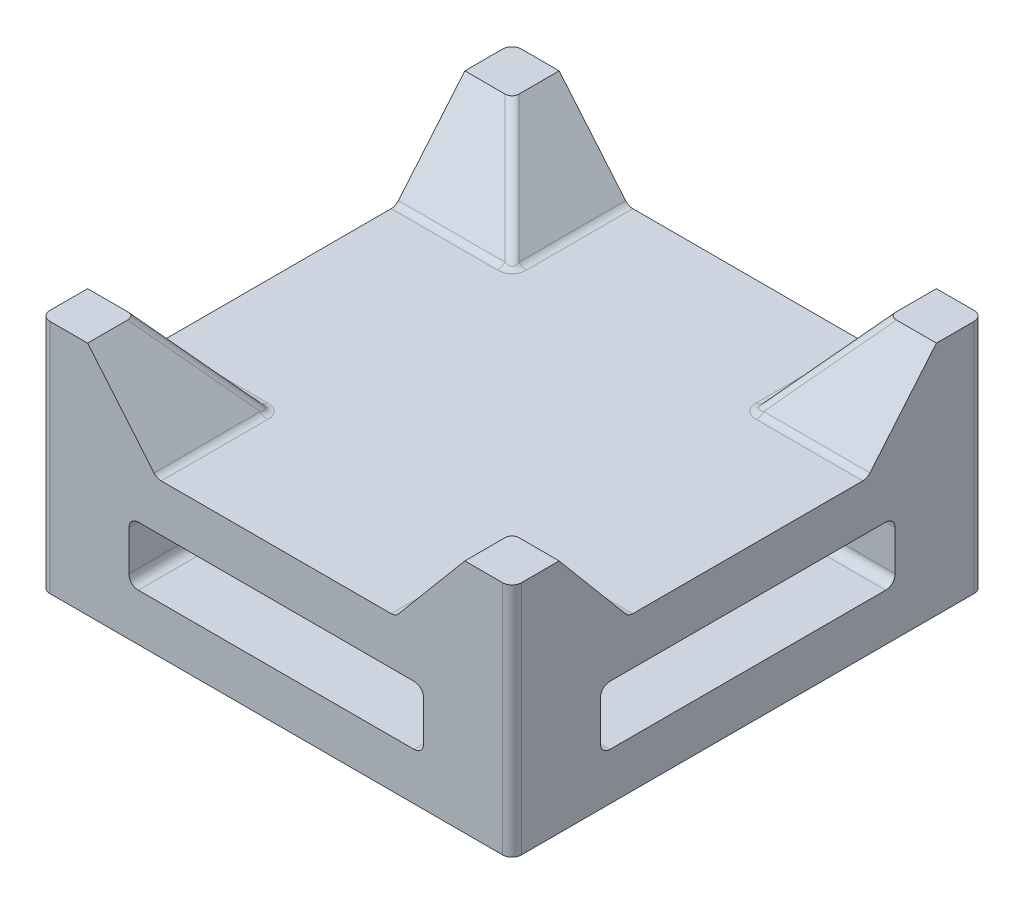
SolidWorks part; units mm, degrees
ref_plane "Front" through (0, 0, 0) normal (0, 0, 1) x (1, 0, 0)
ref_plane "Top" through (0, 0, 0) normal (0, 1, 0) x (1, 0, 0)
ref_plane "Right" through (0, 0, 0) normal (1, 0, 0) x (0, 0, -1)
sketch "Sketch1" plane through (0, 0, 0) normal (0, 1, 0) x (1, 0, 0)
  line L1 (12.7, -12.7) -> (-12.7, -12.7)
  line L2 (12.7, -12.7) -> (12.7, 12.7)
  line L3 (12.7, 12.7) -> (-12.7, 12.7)
  line L4 (-12.7, -12.7) -> (-12.7, 12.7)
  line L5 (12.7, -12.7) -> (-12.7, 12.7) construction
  line L6 (12.7, 12.7) -> (-12.7, -12.7) construction
  point P0 (0, 0)
  dimension "D1" = 25.4
extrude "Boss-Extrude1" add sketch "Sketch1" along normal blind 12.7
sketch "Sketch2" plane through (0, 0, 0) normal (0, 0, 1) x (1, 0, 0)
  line L0 (-10.16, 12.7) -> (-6.4302, 8.255)
  line L1 (-12.7, 12.7) -> (12.7, 12.7) construction
  line L2 (-6.4302, 8.255) -> (6.4302, 8.255)
  line L3 (6.4302, 8.255) -> (10.16, 12.7)
  line L4 (-6.4302, 8.255) -> (-12.7, 8.255) construction
  line L5 (-12.7, 12.7) -> (-12.7, 0) construction
  line L6 (6.4302, 8.255) -> (12.7, 8.255) construction
  line L7 (12.7, 12.7) -> (12.7, 0) construction
  line L8 (-7.9375, 5.715) -> (-12.7, 5.715) construction
  line L9 (-7.9375, 5.715) -> (7.9375, 5.715)
  line L10 (-7.9375, 5.715) -> (-7.9375, 2.54)
  line L11 (-7.9375, 2.54) -> (7.9375, 2.54)
  line L12 (7.9375, 5.715) -> (7.9375, 2.54)
  line L13 (7.9375, 5.715) -> (12.7, 5.715) construction
  line L14 (-12.7, 0) -> (12.7, 0) construction
  line L15 (-10.16, 12.7) -> (10.16, 12.7)
  dimension "D1" = 50
  dimension "D2" = 3.175
  dimension "D3" = 2.54
  dimension "D4" = 2.54
  dimension "D5" = 2.54
  dimension "D6" = 15.875
extrude "Cut-Extrude1" cut sketch "Sketch2" against normal through all both and the other way through all
sketch "Sketch3" plane through (0, 0, 0) normal (1, 0, 0) x (0, 0, -1)
  line L0 (-10.16, 12.7) -> (-6.4302, 8.255)
  line L1 (-7.9375, 5.715) -> (7.9375, 5.715)
  line L2 (-7.9375, 5.715) -> (-7.9375, 2.54)
  line L3 (-7.9375, 2.54) -> (7.9375, 2.54)
  line L4 (7.9375, 5.715) -> (7.9375, 2.54)
  line L5 (-12.7, 12.7) -> (12.7, 12.7) construction
  line L6 (-6.4302, 8.255) -> (6.4302, 8.255)
  line L7 (6.4302, 8.255) -> (10.16, 12.7)
  line L8 (-12.7, 12.7) -> (-12.7, 0) construction
  line L14 (-10.16, 12.7) -> (10.16, 12.7)
  dimension "D1" = 50
  dimension "D2" = 2.54
  dimension "D3" = 15.875
extrude "Cut-Extrude2" cut sketch "Sketch3" against normal through all both and the other way through all
sketch "Sketch4" plane through (0, 0, 0) normal (0, 0, 1) x (1, 0, 0)
  line L0 (-6.35, -3.175) -> (6.35, -3.175)
  line L1 (6.35, -3.175) -> (6.35, -4.7625)
  line L2 (6.35, -4.7625) -> (3.175, -7.9375)
  line L3 (3.175, -7.9375) -> (-3.175, -7.9375)
  line L4 (-3.175, -7.9375) -> (-6.35, -4.7625)
  line L5 (-6.35, -4.7625) -> (-6.35, -3.175)
  line L6 (0, 0) -> (0, -3.175) construction
  line L7 (-12.7, 0) -> (12.7, 0) construction
  point P10 (-6.35, -4.2321)
  dimension "D1" = 12.7
  dimension "D2" = 7.9375
  dimension "D3" = 3.175
  dimension "D4" = 45
  dimension "D5" = 3.175
extrude "Boss-Extrude2" add sketch "Sketch4" along normal mid plane 6.35 separate body
sketch "Sketch5" plane through (0, 0, 0) normal (0, -1, 0) x (1, 0, 0)
  line L0 (-3.175, 3.175) -> (3.175, 3.175) construction
  line L1 (3.175, -3.175) -> (0, -3.175)
  line L2 (3.175, -3.175) -> (3.175, 0)
  line L3 (0, 3.175) -> (-3.175, 3.175)
  line L4 (-3.175, 0) -> (-3.175, 3.175)
  line L5 (3.175, -3.175) -> (-3.175, 3.175) construction
  line L6 (3.175, 3.175) -> (-3.175, -3.175) construction
  arc A0 (0, -3.175) -> (-3.175, 0) centre (0, 0) cw
  arc A1 (3.175, 0) -> (0, 3.175) centre (0, 0) ccw
  point P0 (0, 0)
  point P14 (0, 0)
extrude "Boss-Extrude3" add sketch "Sketch5" along normal up to next
fillet "Fillet1" radius 1.27 4 edges at (7.9375, 4.1275, 7.9375) (7.9375, 4.1275, -7.9375) (-7.9375, 4.1275, -7.9375) (-7.9375, 4.1275, 7.9375)
fillet "Fillet2" radius 0.508 40 edges at (6.4302, 8.255, 9.5651) (9.5651, 8.255, -6.4302) (-6.4302, 8.255, -9.5651) (-9.5651, 8.255, 6.4302) (-7.9375, 5.715, 10.9537) (-10.9538, 5.715, 7.9375) (-10.9538, 2.54, 7.9375) (-7.9375, 2.54, 10.9537) (-7.9375, 2.54, -10.9538) (-10.9538, 2.54, -7.9375) (-10.9538, 5.715, -7.9375) (-7.9375, 5.715, -10.9538) (7.9375, 5.715, -10.9538) (10.9537, 5.715, -7.9375) (10.9537, 2.54, -7.9375) (7.9375, 2.54, -10.9537) (7.9375, 2.54, 10.9537) (10.9537, 2.54, 7.9375) (10.9537, 5.715, 7.9375) (7.9375, 5.715, 10.9537) (-8.3095, 5.715, 8.3095) (-8.3095, 2.54, 8.3095) (-8.3095, 2.54, -8.3095) (-8.3095, 5.715, -8.3095) (8.3095, 5.715, -8.3095) (8.3095, 2.54, -8.3095) (8.3095, 2.54, 8.3095) (8.3095, 5.715, 8.3095) (12.7, 6.35, 12.7) (-12.7, 6.35, 12.7) (12.7, 6.35, -12.7) (-12.7, 6.35, -12.7) (9.5651, 8.255, 6.4302) (8.2951, 10.4775, 8.2951) (6.4302, 8.255, -9.5651) (8.2951, 10.4775, -8.2951) (-9.5651, 8.255, -6.4302) (-8.2951, 10.4775, -8.2951) (-6.4302, 8.255, 9.5651) (-8.2951, 10.4775, 8.2951)
fillet "Fillet3" radius 0.762 10 edges at (3.175, -3.175, -1.5875) (-3.175, -3.175, 1.5875) (-3.175, 0, 1.5875) (1.5875, 0, -3.175) (3.175, 0, -1.5875) (-1.5875, 0, 3.175) (2.2451, -3.175, 2.2451) (-2.2451, -3.175, -2.2451) (-2.2451, 0, -2.2451) (2.2451, 0, 2.2451)
